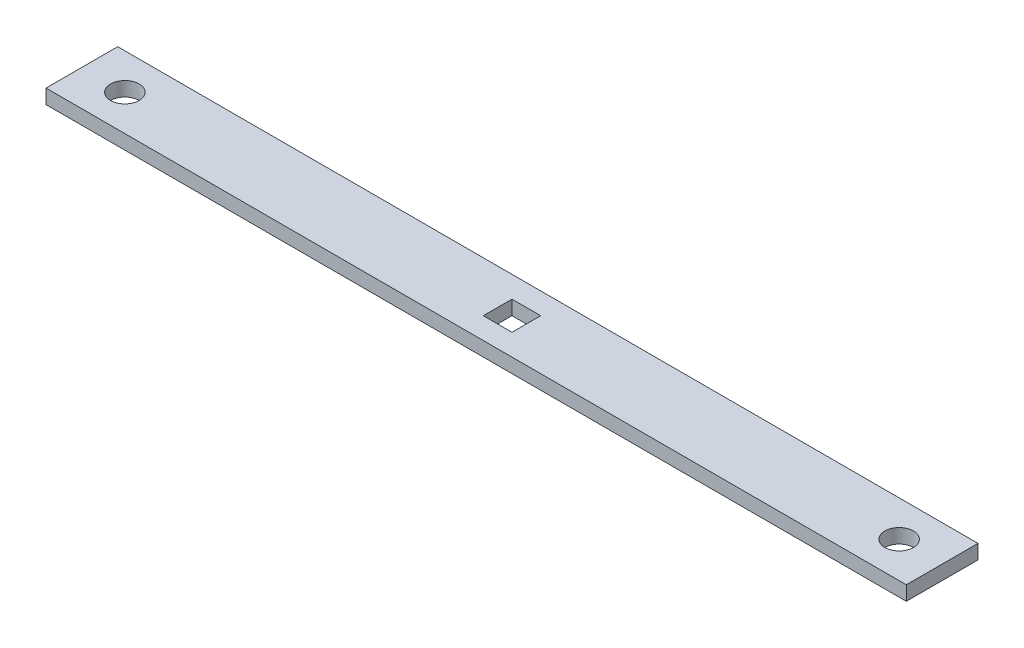
SolidWorks part; units mm, degrees
material "Brass"
ref_plane "Front Plane" through (0, 0, 0) normal (0, 0, 1) x (1, 0, 0)
ref_plane "Top Plane" through (0, 0, 0) normal (0, 1, 0) x (1, 0, 0)
ref_plane "Right Plane" through (0, 0, 0) normal (1, 0, 0) x (0, 0, -1)
sketch "Sketch2" plane through (0, 0, 0) normal (0, 1, 0) x (1, 0, 0)
  line L1 (-15, -1.25) -> (15, -1.25)
  line L2 (-15, -1.25) -> (-15, 1.25)
  line L3 (-15, 1.25) -> (15, 1.25)
  line L4 (15, -1.25) -> (15, 1.25)
  line L5 (-15, -1.25) -> (15, 1.25) construction
  line L6 (-15, 1.25) -> (15, -1.25) construction
  point P0 (0, 0)
  dimension "D1" = 2.5
  dimension "D2" = 30
extrude "Boss-Extrude1" add sketch "Sketch2" along normal blind 0.5
sketch "Sketch3" plane through (0, 0.5, 0) normal (0, 1, 0) x (1, 0, 0)
  line L1 (-0.5, -0.5) -> (0.5, -0.5)
  line L2 (-0.5, -0.5) -> (-0.5, 0.5)
  line L3 (-0.5, 0.5) -> (0.5, 0.5)
  line L4 (0.5, -0.5) -> (0.5, 0.5)
  line L5 (-0.5, -0.5) -> (0.5, 0.5) construction
  line L6 (-0.5, 0.5) -> (0.5, -0.5) construction
  circle A0 centre (-13.5, 0) radius 0.5
  circle A1 centre (13.5, 0) radius 0.5
  point P4 (0, 0)
  dimension "D1" = 1
  dimension "D4" = 1
  dimension "D2" = 13.5
  dimension "D3" = 13.5
  dimension "D5" = 1
extrude "Cut-Extrude1" cut sketch "Sketch3" against normal through all both and the other way through all
scale "Scale1" scale about centroid uniform scaling yes scale factor 6
